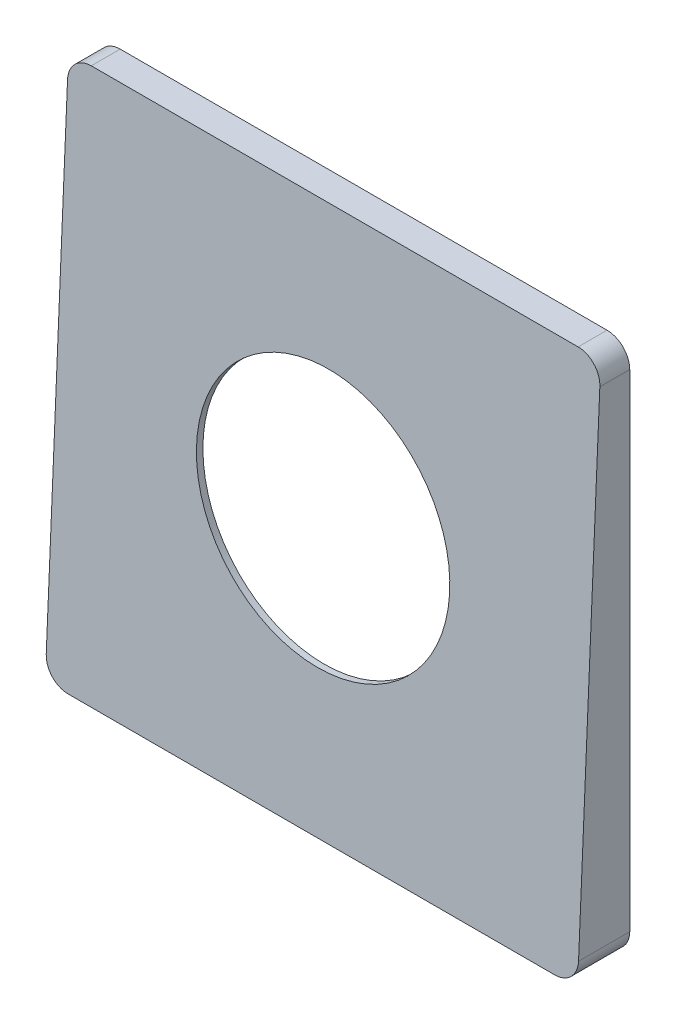
SolidWorks part; units mm, degrees
ref_plane "Front Plane" through (0, 0, 0) normal (0, 0, 1) x (1, 0, 0)
ref_plane "Top Plane" through (0, 0, 0) normal (0, 1, 0) x (1, 0, 0)
ref_plane "Right Plane" through (0, 0, 0) normal (1, 0, 0) x (0, 0, -1)
sketch "Sketch1" plane through (0, 0, 0) normal (0, 0, 1) x (1, 0, 0)
  line L0 (-38.566, 0) -> (72.4153, 0) construction
  line L1 (0, -49.5581) -> (0, 74.5126) construction
  line L2 (-37.5, 40) -> (37.5, 40)
  line L3 (-40, 37.5) -> (-40, -37.5)
  line L4 (-37.5, -40) -> (37.5, -40)
  line L5 (40, 37.5) -> (40, -37.5)
  arc A0 (-40, -37.5) -> (-37.5, -40) centre (-37.5, -37.5) ccw
  arc A1 (37.5, -40) -> (40, -37.5) centre (37.5, -37.5) ccw
  arc A2 (37.5, 40) -> (40, 37.5) centre (37.5, 37.5) cw
  arc A3 (-37.5, 40) -> (-40, 37.5) centre (-37.5, 37.5) ccw
  dimension "D3" = 2.5
  dimension "D1" = 80
  dimension "D2" = 80
  dimension "D4" = 40
  dimension "D5" = 40
extrude "Extrude-Thin1" add sketch "Sketch1" along normal blind 8 thin thin type one direction wall 1
sketch "Sketch5" plane through (41, 0, 0) normal (1, 0, 0) x (0, 0, -1)
  line L0 (20.3178, 0) -> (-25.0092, 0) construction
  line L1 (0, 43.59) -> (0, -45.2443) construction
  line L2 (-3.4562, 41) -> (-8, 41)
  line L3 (-8, 41) -> (-8, -41)
  line L4 (-8, -41) -> (-7.0437, -41)
  line L6 (-7.0437, -41) -> (-3.4562, 41)
  line L7 (-8, -41) -> (0, -41) construction
  line L11 (-8, 41) -> (0, 41) construction
extrude "Cut-Extrude2" cut sketch "Sketch5" against normal blind 120
sketch "Sketch6" plane through (41, 0, 0) normal (1, 0, 0) x (0, 0, -1)
  line L0 (-7.0437, -41) -> (-3.4562, 41)
  line L1 (-3.4562, 41) -> (-4.4572, 41)
  line L2 (-4.4572, 41) -> (-8.0447, -41)
  line L3 (-8.0447, -41) -> (-7.0437, -41)
  line L4 (-3.4562, 41) -> (-3.4562, 45.0301) construction
  dimension "D1" = 1
  dimension "D2" = 90
extrude "Boss-Extrude1" add sketch "Sketch6" against normal blind 82
sketch "Sketch7" plane through (0, 0, 0) normal (0, 0, -1) x (-1, 0, 0)
  line L0 (0, 0) -> (0, 69.537) construction
  line L1 (71.0569, 0) -> (20.5255, 0) construction
  line L2 (-37.5, 41) -> (37.5, 41)
  line L3 (-37.5, 41) -> (37.5, 41) construction
  line L4 (-41, -37.5) -> (-41, 37.5)
  line L5 (41, -37.5) -> (41, 37.5)
  line L6 (-41, -37.5) -> (-41, 37.5) construction
  line L7 (-37.5, -41) -> (37.5, -41)
  arc A0 (37.5, 41) -> (41, 37.5) centre (37.5, 37.5) cw
  arc A1 (-37.5, -41) -> (-41, -37.5) centre (-37.5, -37.5) cw
  arc A2 (37.5, -41) -> (41, -37.5) centre (37.5, -37.5) ccw
  arc A4 (-37.5, 41) -> (-41, 37.5) centre (-37.5, 37.5) ccw
  point P9 (0, -41)
  point P13 (-41, 0)
  point P14 (0, 41)
  point P25 (41, 0)
extrude "Cut-Extrude-Thin1" cut sketch "Sketch7" against normal blind 82 thin thin type one direction wall 11
sketch "Sketch8" plane through (0, 0.273, 6.239) normal (0, 0.0437, 0.999) x (1, 0, 0)
  line L0 (0, 0) -> (0, 28.9526) construction
  line L1 (23.1598, 0) -> (-27.4609, 0) construction
  circle A0 centre (0, 0) radius 19.5
  dimension "D1" = 39
extrude "Cut-Extrude3" cut sketch "Sketch8" against normal blind 82
